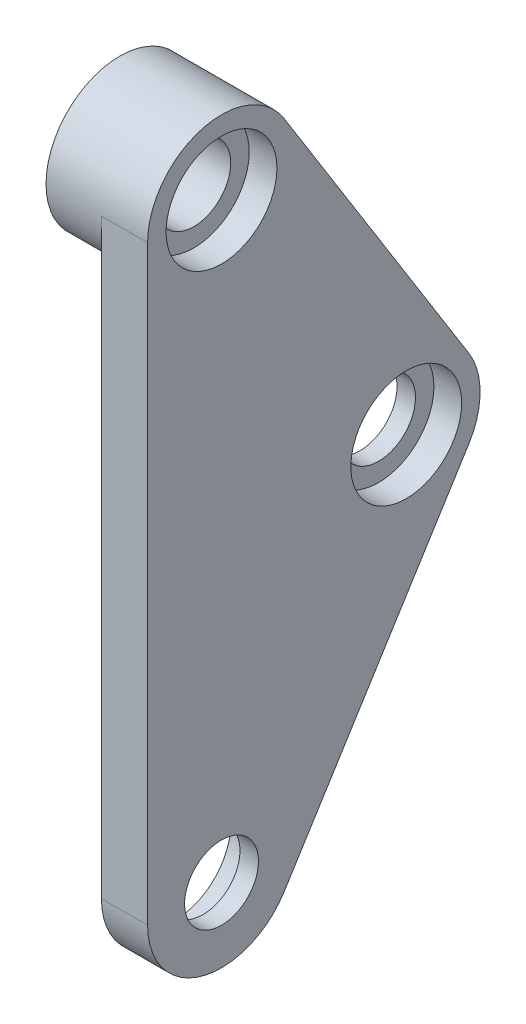
SolidWorks part; units mm, degrees
ref_plane "前视基准面" through (0, 0, 0) normal (0, 0, 1) x (1, 0, 0)
ref_plane "上视基准面" through (0, 0, 0) normal (0, 1, 0) x (1, 0, 0)
ref_plane "右视基准面" through (0, 0, 0) normal (1, 0, 0) x (0, 0, -1)
other "Configuration Table"
sketch "草图1" plane through (0, 0, 0) normal (1, 0, 0) x (0, 0, -1)
  line L0 (0, -20) -> (18, -20) construction
  line L1 (0, 0) -> (18, 0) construction
  line L2 (0, 0) -> (0, -40)
  line L3 (0, -40) -> (18, -40) construction
  line L4 (18, 0) -> (18, -40) construction
  line L5 (7.392, -1.88) -> (17.392, -17.88)
  line L6 (17.392, -22.12) -> (7.392, -38.12)
  circle A0 centre (4, -4) radius 4
  circle A1 centre (4, -36) radius 4
  circle A2 centre (14, -20) radius 4
  circle A3 centre (4, -4) radius 2
  circle A4 centre (14, -20) radius 2
  circle A5 centre (4, -36) radius 2
  dimension "D1" = 8
  dimension "D2" = 4
  dimension "D3" = 40
  dimension "D4" = 18
extrude "凸台-拉伸1" add sketch "草图1" along normal blind 2.5 contours A2 L5 A0 L2 A1 L6 | A0 | A2 | A1 region at (0, -20, -6.5849)
extrude "凸台-拉伸2" add sketch "草图1<4>" against normal blind 3 contours A0
sketch "草图1<4>" plane through (0, 0, 0) normal (1, 0, 0) x (0, 0, -1) same geometry as "草图1"
extrude "切除-拉伸1" cut sketch "草图1<3>" along normal through all both and the other way through all contours A3 | A4 | A5
sketch "草图1<3>" plane through (0, 0, 0) normal (1, 0, 0) x (0, 0, -1) same geometry as "草图1"
sketch "草图2" plane through (2.5, 0, 0) normal (1, 0, 0) x (0, 0, -1)
  circle A0 centre (4, -4) radius 3
  circle A1 centre (14, -20) radius 3
  circle A2 centre (4, -36) radius 3
  circle M3 centre (4, -4) radius 2
  arc M9 (7.392, -1.88) -> (0, -4) centre (4, -4) ccw
  dimension "D1" = 6
extrude "切除-拉伸2" cut sketch "草图2" against normal blind 1.5 contours A0 M9 M3 | A1 region at (2.5, -4, -1.0849)
extrude "切除-拉伸3" cut sketch "草图2<3>" along normal blind 1.5 from surface contours A2 starting at face at (0, -20, -16)
sketch "草图2<3>" plane through (2.5, 0, 0) normal (1, 0, 0) x (0, 0, -1) same geometry as "草图2"
ref_plane "基准面1" through (-10, 0, 0) normal (1, 0, 0) x (0, 0, -1)
mirror "镜向2" about plane through (-10, 0, 0) normal (1, 0, 0) of bodies 111 109
sketch "草图3" plane through (0, 0, 0) normal (0, 0, 1) x (1, 0, 0)
  line L1 (-30.2525, 5.5451) -> (-9.9257, 5.5451)
  line L2 (-30.2525, 5.5451) -> (-30.2525, -46.6048)
  line L3 (-30.2525, -46.6048) -> (-9.9257, -46.6048)
  line L4 (-9.9257, 5.5451) -> (-9.9257, -46.6048)
extrude "切除-拉伸4" cut sketch "草图3" against normal through all
